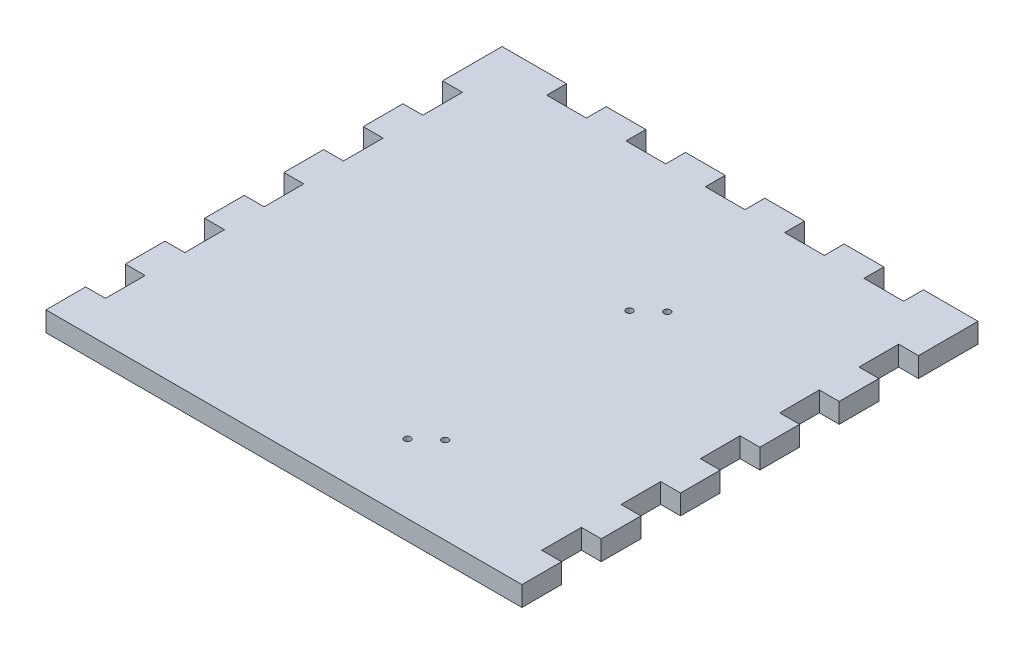
SolidWorks part; units mm, degrees
ref_plane "Front Plane" through (0, 0, 0) normal (0, 0, 1) x (1, 0, 0)
ref_plane "Top Plane" through (0, 0, 0) normal (0, 1, 0) x (1, 0, 0)
ref_plane "Right Plane" through (0, 0, 0) normal (1, 0, 0) x (0, 0, -1)
sketch "Sketch1" plane through (0, 0, 0) normal (0, 1, 0) x (1, 0, 0)
  line L1 (-139.7, -139.7) -> (139.7, -139.7)
  line L2 (-139.7, -139.7) -> (-139.7, 139.7)
  line L3 (-139.7, 139.7) -> (139.7, 139.7)
  line L4 (139.7, -139.7) -> (139.7, 139.7)
  line L5 (-139.7, -139.7) -> (139.7, 139.7) construction
  line L6 (-139.7, 139.7) -> (139.7, -139.7) construction
  point P0 (0, 0)
  dimension "D1" = 279.4
  dimension "D2" = 279.4
extrude "Boss-Extrude1" add sketch "Sketch1" along normal blind 12.7
sketch "Sketch2" plane through (139.7, 0, 0) normal (1, 0, 0) x (0, 0, -1)
  line L0 (-139.7, 12.7) -> (139.7, 12.7) construction
  line L1 (-139.7, 0) -> (-114.3, 0)
  line L2 (-139.7, 0) -> (-139.7, 12.7)
  line L3 (-139.7, 12.7) -> (-114.3, 12.7)
  line L4 (-114.3, 0) -> (-114.3, 12.7)
  dimension "D1" = 25.4
extrude "Boss-Extrude2" add sketch "Sketch2" along normal blind 12.7
pattern_linear "LPattern1" count 6 spacing 50.8 along (0, 0, -1) of "Boss-Extrude2"
mirror "Mirror1" about plane through (0, 0, 0) normal (1, 0, 0) of "LPattern1"
sketch "Sketch3" plane through (0, 0, -139.7) normal (0, 0, -1) x (-1, 0, 0)
  line L0 (-152.4, 12.7) -> (152.4, 12.7) construction
  line L1 (-142.875, 12.7) -> (-117.475, 12.7)
  line L2 (-142.875, 12.7) -> (-142.875, 0)
  line L3 (-142.875, 0) -> (-117.475, 0)
  line L4 (-117.475, 12.7) -> (-117.475, 0)
  line L5 (-152.4, 0) -> (152.4, 0) construction
  line L6 (-152.4, 0) -> (-152.4, 12.7) construction
  dimension "D1" = 9.525
  dimension "D2" = 25.4
extrude "Boss-Extrude3" add sketch "Sketch3" along normal blind 12.7
pattern_linear "LPattern2" count 6 spacing 50.8 along (-1, 0, 0) of "Boss-Extrude3"
sketch "Sketch5" plane through (0, 0, -139.7) normal (0, 0, -1) x (-1, 0, 0)
  line L11 (160.655, 0) -> (-160.655, 0) construction
  line L12 (-152.4, 12.7) -> (-127, 12.7)
  line L13 (-152.4, 12.7) -> (-152.4, 0)
  line L14 (-152.4, 0) -> (-127, 0)
  line L15 (-127, 12.7) -> (-127, 0)
  dimension "D1" = 25.4
extrude "Boss-Extrude4" add sketch "Sketch5" along normal blind 12.7
mirror "Mirror2" about plane through (0, 0, 0) normal (1, 0, 0) of "Boss-Extrude4"
sketch "Sketch6" plane through (0, 12.7, 0) normal (0, 1, 0) x (1, 0, 0)
  circle A0 centre (34.925, -95.5244) radius 2.1
  circle A1 centre (47.625, -84.0944) radius 2.1
  circle A2 centre (47.625, 58.1456) radius 2.1
  circle A3 centre (34.925, 46.6818) radius 2.1338
extrude "Cut-Extrude1" cut sketch "Sketch6" against normal through all
sketch "Sketch7" plane through (0, 0, 0) normal (0, -1, 0) x (1, 0, 0)
  circle A0 centre (47.625, -58.1456) radius 5.08
  circle A1 centre (34.925, -46.6818) radius 5.08
  circle A2 centre (47.625, 84.2002) radius 5.08
  circle A3 centre (34.925, 95.5244) radius 5.08
  dimension "D1" = 10.16
  dimension "D2" = 10.16
  dimension "D3" = 10.16
  dimension "D4" = 10.16
extrude "Cut-Extrude2" cut sketch "Sketch7" against normal blind 6.35
